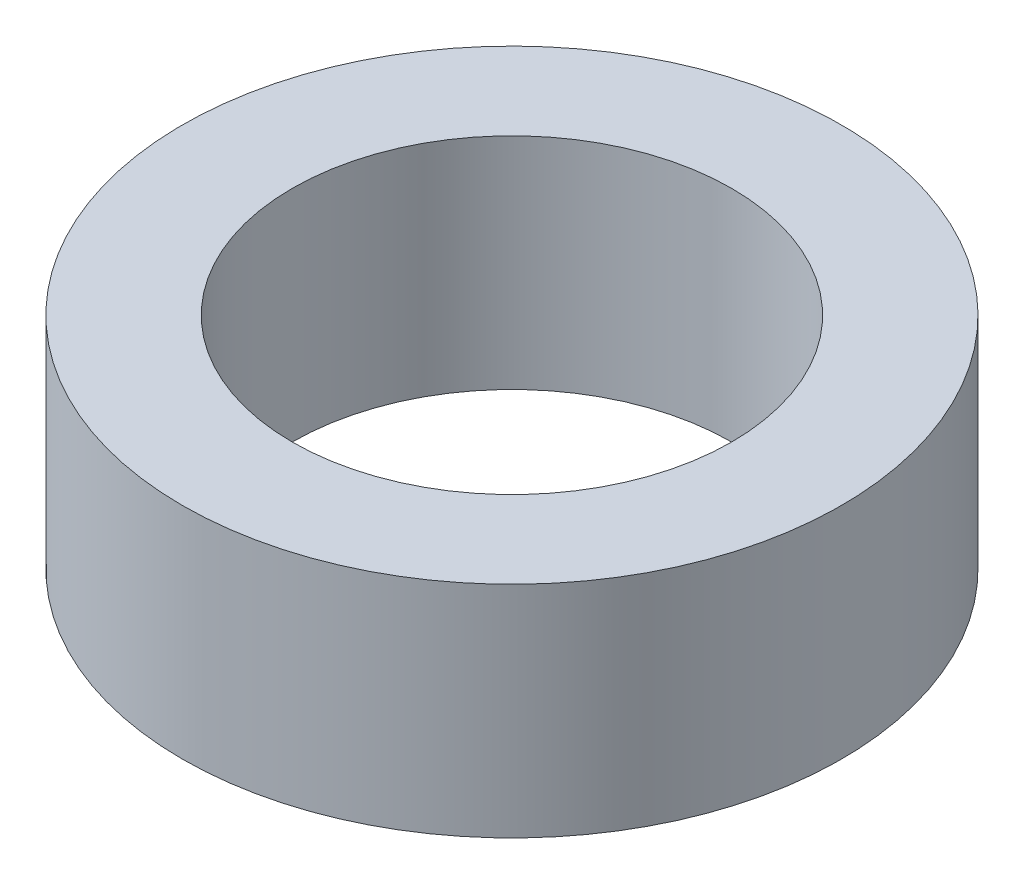
SolidWorks part; units mm, degrees
ref_plane "Front Plane" through (0, 0, 0) normal (0, 0, 1) x (1, 0, 0)
ref_plane "Top Plane" through (0, 0, 0) normal (0, 1, 0) x (1, 0, 0)
ref_plane "Right Plane" through (0, 0, 0) normal (1, 0, 0) x (0, 0, -1)
sketch "Sketch1" plane through (0, 0, 0) normal (0, 1, 0) x (1, 0, 0)
  circle A0 centre (0, 0) radius 37.5
  dimension "FLANGE_OD" = 75
extrude "Boss-Extrude1" add sketch "Sketch1" along normal blind 25
sketch "Sketch2" plane through (0, 0, 0) normal (0, 1, 0) x (1, 0, 0)
  circle A0 centre (0, 0) radius 25
  dimension "BORE_D" = 50
extrude "Cut-Extrude1" cut sketch "Sketch2" along normal through all
sketch "Sketch3" plane through (0, 25, 0) normal (0, 1, 0) x (1, 0, 0)
  circle A0 centre (0, 0) radius 14.8795 construction
  circle A1 centre (-14.8795, 0) radius 2.0293
  dimension "BOLT_D" = 4.0586
  dimension "BOLT_PCD" = 29.759
extrude "Cut-Extrude2" cut sketch "Sketch3" against normal blind 20.2656 rebuild error yes
pattern_circular "CirPattern1" count 3 over 360 rebuild error yes
